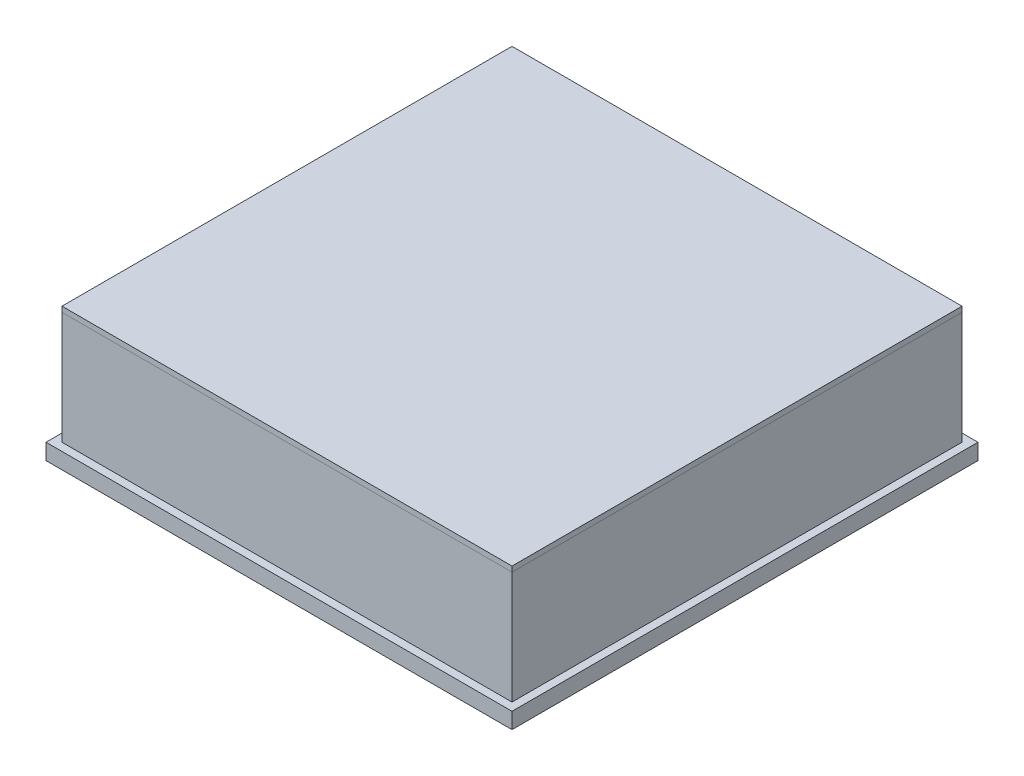
SolidWorks part; units mm, degrees
ref_plane "Front Plane" through (0, 0, 0) normal (0, 0, 1) x (1, 0, 0)
ref_plane "Top Plane" through (0, 0, 0) normal (0, 1, 0) x (1, 0, 0)
ref_plane "Right Plane" through (0, 0, 0) normal (1, 0, 0) x (0, 0, -1)
sketch "Sketch2" plane through (0, 0, 0) normal (0, 1, 0) x (1, 0, 0)
  line L0 (-4304.792, -4304.792) -> (-4304.792, 4304.792)
  line L1 (3999.992, -3999.992) -> (-3999.992, -3999.992)
  line L2 (3999.992, -3999.992) -> (3999.992, 3999.992)
  line L3 (3999.992, 3999.992) -> (-3999.992, 3999.992)
  line L4 (-3999.992, -3999.992) -> (-3999.992, 3999.992)
  line L5 (3999.992, -3999.992) -> (-3999.992, 3999.992) construction
  line L6 (3999.992, 3999.992) -> (-3999.992, -3999.992) construction
  line L7 (4304.792, 4304.792) -> (-4304.792, 4304.792)
  line L8 (4304.792, -4304.792) -> (4304.792, 4304.792)
  line L9 (4304.792, -4304.792) -> (-4304.792, -4304.792)
  point P0 (0, 0)
  dimension "D1" = 7999.984
  dimension "D2" = 7999.984
  dimension "D3" = 304.8
extrude "Boss-Extrude1" add sketch "Sketch2" along normal blind 1999.996
sketch "Sketch3" plane through (0, 0, 0) normal (0, -1, 0) x (1, 0, 0)
  line L0 (-4304.792, -4304.792) -> (-4304.792, 4304.792) construction
  line L1 (-4304.792, -4304.792) -> (-4304.792, 4304.792)
  line L2 (4304.792, -4304.792) -> (-4304.792, -4304.792) construction
  line L3 (4304.792, 4304.792) -> (4304.792, -4304.792) construction
  line L4 (-4304.792, 4304.792) -> (4304.792, 4304.792) construction
  line L5 (4304.792, -4304.792) -> (-4304.792, -4304.792)
  line L6 (4304.792, 4304.792) -> (4304.792, -4304.792)
  line L7 (-4304.792, 4304.792) -> (4304.792, 4304.792)
extrude "Boss-Extrude2" add sketch "Sketch3" along normal blind 152.4
sketch "Sketch4" plane through (0, -152.4, 0) normal (0, -1, 0) x (1, 0, 0)
  line L30 (-4457.192, 4457.192) -> (-4457.192, -4457.192)
  line L31 (-4457.192, -4457.192) -> (4457.192, -4457.192)
  line L32 (4457.192, -4457.192) -> (4457.192, 4457.192)
  line L33 (4457.192, 4457.192) -> (-4457.192, 4457.192)
  line L34 (-4457.192, 4457.192) -> (-4457.192, -4457.192)
  line L35 (-4457.192, -4457.192) -> (4457.192, -4457.192)
  line L36 (4457.192, -4457.192) -> (4457.192, 4457.192)
  line L37 (4457.192, 4457.192) -> (-4457.192, 4457.192)
  line L43 (3847.592, 3847.592) -> (-3847.592, 3847.592)
  line L44 (-3847.592, 3847.592) -> (-3847.592, -3847.592)
  line L45 (-3847.592, -3847.592) -> (3847.592, -3847.592)
  line L46 (3847.592, -3847.592) -> (3847.592, 3847.592)
  line L47 (3847.592, 3847.592) -> (-3847.592, 3847.592)
  line L48 (-3847.592, 3847.592) -> (-3847.592, -3847.592)
  line L49 (-3847.592, -3847.592) -> (3847.592, -3847.592)
  line L50 (3847.592, -3847.592) -> (3847.592, 3847.592)
  dimension "D1" = 152.4
  dimension "D2" = 152.4
extrude "Boss-Extrude3" add sketch "Sketch4" along normal blind 304.8
sketch "Sketch6" plane through (0, 0, 0) normal (0, 1, 0) x (1, 0, 0)
  line L0 (0, 0) -> (-3999.992, 3999.992) construction
  line L6 (-3999.992, 1656.8509) -> (-1656.8509, 1656.8509) construction
  line L7 (-3999.992, 3999.992) -> (-3999.992, -3999.992) construction
  line L19 (-1656.8509, 1656.8509) -> (-1656.8509, 3999.992) construction
  line L20 (3999.992, 3999.992) -> (-3999.992, 3999.992) construction
  line L22 (-1656.8509, 1656.8509) -> (0, 0) construction
  line L24 (1809.2509, 1504.4509) -> (1809.2509, 1809.2509)
  line L25 (-1504.4509, 1809.2509) -> (-1809.2509, 1809.2509)
  line L29 (-1504.4509, 1809.2509) -> (-1504.4509, 1504.4509)
  line L30 (-1504.4509, 1504.4509) -> (-1809.2509, 1504.4509)
  line L31 (-1809.2509, 1809.2509) -> (-1809.2509, 1504.4509)
  line L32 (-1504.4509, 1809.2509) -> (-1809.2509, 1504.4509) construction
  line L33 (-1504.4509, 1504.4509) -> (-1809.2509, 1809.2509) construction
  line L34 (1809.2509, 1809.2509) -> (1504.4509, 1809.2509)
  line L35 (1504.4509, 1504.4509) -> (1504.4509, 1809.2509)
  line L36 (1809.2509, 1504.4509) -> (1504.4509, 1504.4509)
  line L37 (1504.4509, -1809.2509) -> (1809.2509, -1809.2509)
  line L38 (1809.2509, -1809.2509) -> (1809.2509, -1504.4509)
  line L39 (1504.4509, -1504.4509) -> (1809.2509, -1504.4509)
  line L40 (1504.4509, -1809.2509) -> (1504.4509, -1504.4509)
  line L41 (-1809.2509, -1504.4509) -> (-1809.2509, -1809.2509)
  line L42 (-1809.2509, -1809.2509) -> (-1504.4509, -1809.2509)
  line L43 (-1504.4509, -1504.4509) -> (-1504.4509, -1809.2509)
  line L44 (-1809.2509, -1504.4509) -> (-1504.4509, -1504.4509)
  point P30 (0, 0)
  dimension "D1" = 304.8
extrude "Boss-Extrude5" add sketch "Sketch6" along normal up to surface (1999.996 mm away) contours L25 L31 L30 L29 | L36 L24 L34 L35 | L40 L37 L38 L39 | L44 L41 L42 L43 region at (1656.8509, 0, -1656.8509) region at (-1656.8509, 0, -1656.8509) region at (1656.8509, 0, 1656.8509) region at (-1656.8509, 0, 1656.8509) up to face at (0, 1999.996, 0)
sketch "Sketch7" plane through (0, 1999.996, 0) normal (0, 1, 0) x (1, 0, 0)
  line L1 (4304.792, -4304.792) -> (-4304.792, -4304.792)
  line L2 (4304.792, -4304.792) -> (4304.792, 4304.792)
  line L3 (4304.792, 4304.792) -> (-4304.792, 4304.792)
  line L4 (-4304.792, -4304.792) -> (-4304.792, 4304.792)
  line L5 (4304.792, -4304.792) -> (-4304.792, 4304.792) construction
  line L6 (4304.792, 4304.792) -> (-4304.792, -4304.792) construction
  point P0 (0, 0)
extrude "Boss-Extrude6" add sketch "Sketch7" along normal blind 101.6 separate body
